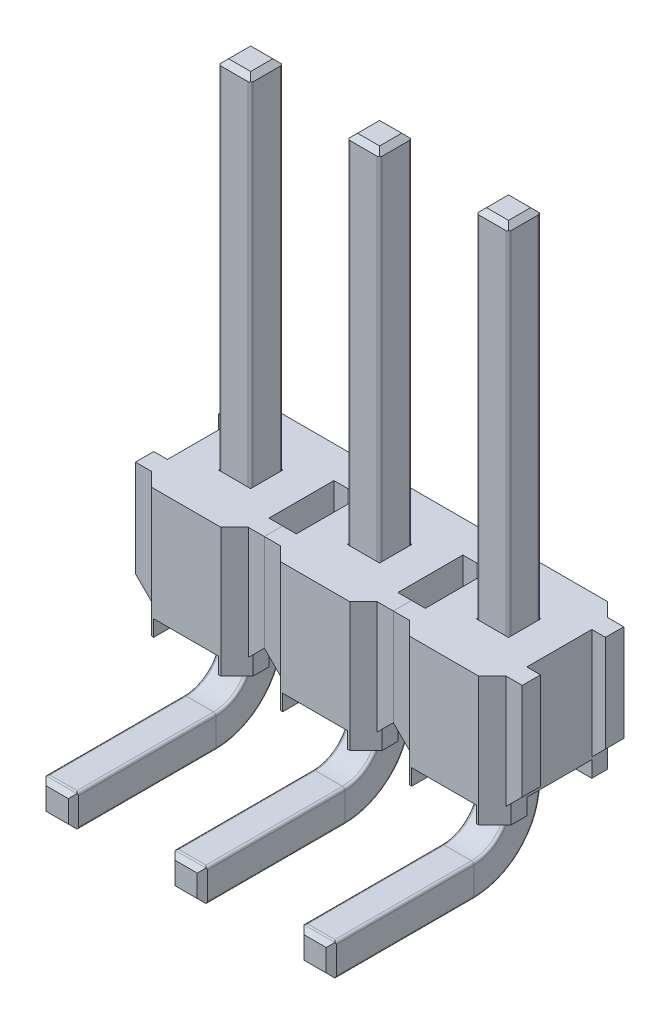
SolidWorks part; units mm, degrees
ref_plane "Alzado" through (0, 0, 0) normal (0, 0, 1) x (1, 0, 0)
ref_plane "Planta" through (0, 0, 0) normal (0, 1, 0) x (1, 0, 0)
ref_plane "Vista lateral" through (0, 0, 0) normal (1, 0, 0) x (0, 0, -1)
sketch "Croquis1" plane through (0, 0, 0) normal (0, 1, 0) x (1, 0, 0)
  line L0 (-1.27, 1) -> (-1, 1)
  line L1 (-1, 1) -> (-1, 1.27)
  line L2 (-1, 1.27) -> (1, 1.27)
  line L3 (1, 1.27) -> (1, 1)
  line L4 (1, 1) -> (1.27, 1)
  line L5 (1.27, 1) -> (1.27, -1)
  line L6 (1.27, -1) -> (1, -1)
  line L7 (1, -1) -> (1, -1.27)
  line L8 (1, -1.27) -> (-1, -1.27)
  line L9 (-1, -1.27) -> (-1, -1)
  line L10 (-1, -1) -> (-1.27, -1)
  line L11 (-1.27, -1) -> (-1.27, 1)
extrude "Saliente-Extruir1" add sketch "Croquis1" along normal blind 2.54
sketch "Croquis2" plane through (0, 0, 0) normal (0, 1, 0) x (1, 0, 0)
  line L1 (-0.3175, 0.3175) -> (0.3175, 0.3175)
  line L2 (-0.3175, 0.3175) -> (-0.3175, -0.3175)
  line L3 (-0.3175, -0.3175) -> (0.3175, -0.3175)
  line L4 (0.3175, 0.3175) -> (0.3175, -0.3175)
extrude "Cortar-Extruir1" cut sketch "Croquis2" along normal blind 4 contours L2 L3 L4 L1
sketch "Croquis3" plane through (0, 0, 0) normal (0, 1, 0) x (1, 0, 0)
  line L1 (-1.3227, 0.64) -> (-1, 0.64)
  line L2 (-1.3227, 0.64) -> (-1.3227, -0.64)
  line L3 (-1.3227, -0.64) -> (-1, -0.64)
  line L4 (-1, 0.64) -> (-1, -0.64)
  line L5 (1, 0.64) -> (1.3183, 0.64)
  line L6 (1, 0.64) -> (1, -0.64)
  line L7 (1, -0.64) -> (1.3183, -0.64)
  line L8 (1.3183, 0.64) -> (1.3183, -0.64)
extrude "Cortar-Extruir2" cut sketch "Croquis3" along normal blind 3
sketch "Croquis4" plane through (0, 0, 0) normal (0, 1, 0) x (1, 0, 0)
  line L1 (-0.64, 1.313) -> (0.64, 1.313)
  line L2 (-0.64, 1.313) -> (-0.64, -1.3257)
  line L3 (-0.64, -1.3257) -> (0.64, -1.3257)
  line L4 (0.64, 1.313) -> (0.64, -1.3257)
extrude "Cortar-Extruir4" cut sketch "Croquis4" along normal blind 0.3175
sketch "Croquis5" plane through (0, 0, 0) normal (0, 1, 0) x (1, 0, 0)
  line L0 (-1, -1) -> (-1, -1.27) construction
  line L1 (-1.3227, 1.092) -> (-1, 1.092)
  line L2 (-1.3227, 1.092) -> (-1.3227, -1.135)
  line L3 (-1.3227, -1.135) -> (-1, -1.135)
  line L4 (-1, 1.092) -> (-1, -1.135)
  line L5 (1, 1) -> (1, 1.27) construction
  line L6 (1, 1.092) -> (1.349, 1.092)
  line L7 (1, 1.092) -> (1, -1.0876)
  line L8 (1, -1.0876) -> (1.349, -1.0876)
  line L9 (1.349, 1.092) -> (1.349, -1.0876)
extrude "Cortar-Extruir5" cut sketch "Croquis5" along normal blind 0.3175
chamfer "Chaflán1" distance 0.3175 angle 45 4 edges at (1.27, 0.3175, -0.82) (1.27, 0.3175, 0.82) (-1.27, 0.3175, 0.82) (-1.27, 0.3175, -0.82)
chamfer "Chaflán2" distance 0.3175 angle 45 4 edges at (-1, 1.27, -1.27) (1, 1.27, -1.27) (-1, 1.27, 1.27) (1, 1.27, 1.27)
sketch "Croquis6" plane through (0, 0, 0) normal (0, 1, 0) x (1, 0, 0)
  line L1 (-1.0766, 0.64) -> (1.1117, 0.64)
  line L2 (-1.0766, 0.64) -> (-1.0766, -0.64)
  line L3 (-1.0766, -0.64) -> (1.1117, -0.64)
  line L4 (1.1117, 0.64) -> (1.1117, -0.64)
extrude "Cortar-Extruir6" cut sketch "Croquis6" along normal blind 0.3175
sketch "Croquis7" plane through (0, 0, 0) normal (0, 1, 0) x (1, 0, 0)
  line L1 (-0.3175, 0.3175) -> (0.3175, 0.3175)
  line L2 (-0.3175, 0.3175) -> (-0.3175, -0.3175)
  line L3 (-0.3175, -0.3175) -> (0.3175, -0.3175)
  line L4 (0.3175, 0.3175) -> (0.3175, -0.3175)
sketch3d "Croquis3D1" plane through (0, 0, 0) normal (0, 0, 1) x (1, 0, 0)
  dimension "D1" = 3.81
sketch "Croquis9" plane through (0, 0, 0) normal (1, 0, 0) x (0, 0, -1)
  line L0 (0, 9.5565) -> (0, -0.27)
  line L1 (-1, -1.27) -> (-3.81, -1.27)
  arc A0 (0, -0.27) -> (-1, -1.27) centre (-1, -0.27) cw
  dimension "D1" = 1
sketch "Croquis10" plane through (0, 0, 3.81) normal (0, 0, 1) x (1, 0, 0)
  line L1 (-0.3175, -0.9525) -> (0.3175, -0.9525)
  line L2 (-0.3175, -0.9525) -> (-0.3175, -1.5875)
  line L3 (-0.3175, -1.5875) -> (0.3175, -1.5875)
  line L4 (0.3175, -0.9525) -> (0.3175, -1.5875)
sweep "Barrer1" add profiles "Croquis10" path "Croquis9"
chamfer "Chaflán6" distance 0.1 angle 45 8 edges at (-0.3175, -1.27, 3.81) (0, -1.5875, 3.81) (0.3175, -1.27, 3.81) (0, -0.9525, 3.81) (0, 9.5565, -0.3175) (0.3175, 9.5565, 0) (-0.3175, 9.5565, 0) (0, 9.5565, 0.3175)
fillet "Redondeo5" radius 0.05 7 edges at (0.3175, 4.5932, 0.3175) (0.3175, -0.7526, 0.5174) (-0.3175, 4.5932, 0.3175) (-0.3175, -0.7526, 0.5174) (0.3175, -0.9525, 2.355) (0, -0.9525, 3.71) (-0.3175, -0.9525, 2.355)
fillet "Redondeo6" radius 0.05 7 edges at (-0.3175, 4.5932, -0.3175) (-0.3175, -1.2016, 0.0684) (0.3175, 4.5932, -0.3175) (0.3175, -1.2016, 0.0684) (-0.3175, -1.5875, 2.355) (0, -1.5875, 3.71) (0.3175, -1.5875, 2.355)
pattern_linear "MatrizL1" count 3 spacing 2.54 along (1, 0, 0) of bodies 107 109
